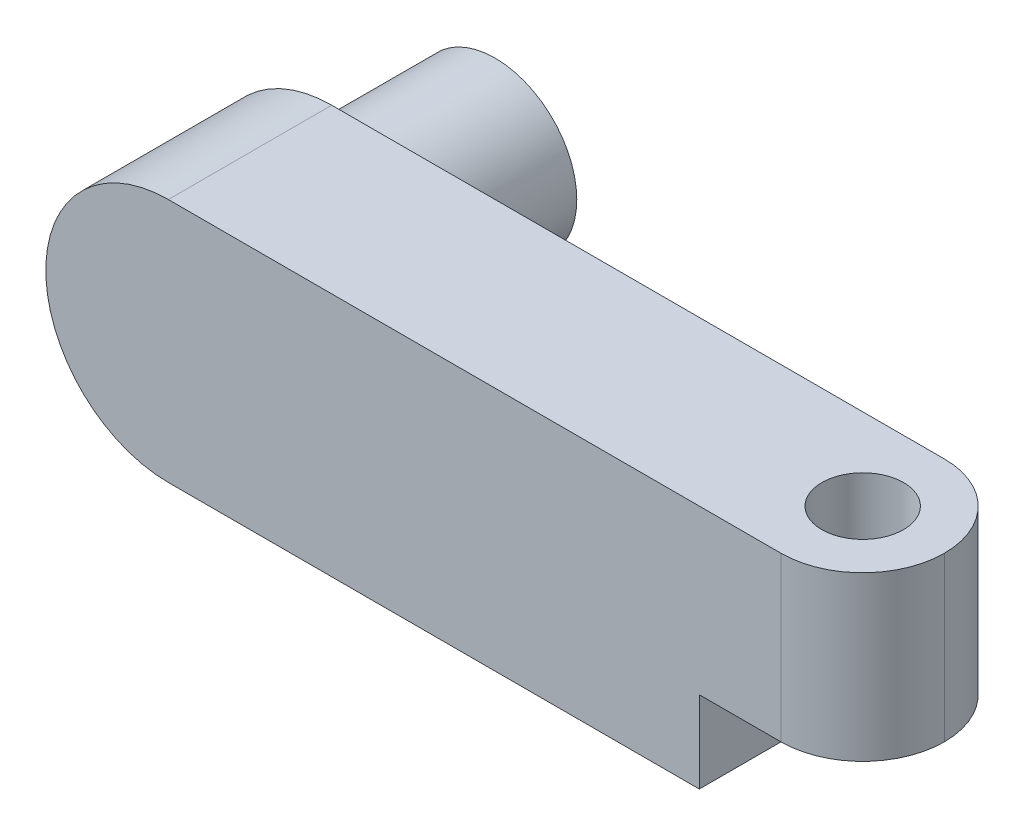
SolidWorks part; units mm, degrees
ref_plane "Front Plane" through (0, 0, 0) normal (0, 0, 1) x (1, 0, 0)
ref_plane "Top Plane" through (0, 0, 0) normal (0, 1, 0) x (1, 0, 0)
ref_plane "Right Plane" through (0, 0, 0) normal (1, 0, 0) x (0, 0, -1)
sketch "Sketch1" plane through (0, 0, 0) normal (0, 0, 1) x (1, 0, 0)
  line L0 (0, 15) -> (85, 15)
  line L2 (0, -15) -> (65, -15)
  line L3 (65, -15) -> (65, -5)
  line L4 (65, -5) -> (85, -5)
  line L5 (85, -5) -> (85, 15)
  arc A0 (0, 15) -> (0, -15) centre (0, 0) ccw
  dimension "D1" = 15
  dimension "D2" = 65
  dimension "D3" = 10
  dimension "D4" = 20
extrude "Boss-Extrude1" add sketch "Sketch1" against normal blind 20 contours L0 L5 L4 L3 L2 A0
fillet "Fillet1" radius 10 2 edges at (85, 5, 0) (85, 5, -20)
sketch "Sketch4" plane through (0, 15, 0) normal (0, 1, 0) x (1, 0, 0)
  circle A0 centre (75, 10) radius 5
  dimension "D1" = 10
extrude "Cut-Extrude1" cut sketch "Sketch4" against normal up to next
sketch "Sketch5" plane through (0, 0, -20) normal (0, 0, -1) x (-1, 0, 0)
  circle A0 centre (0, 0) radius 10
  dimension "D1" = 20
extrude "Boss-Extrude2" add sketch "Sketch5" along normal blind 20
